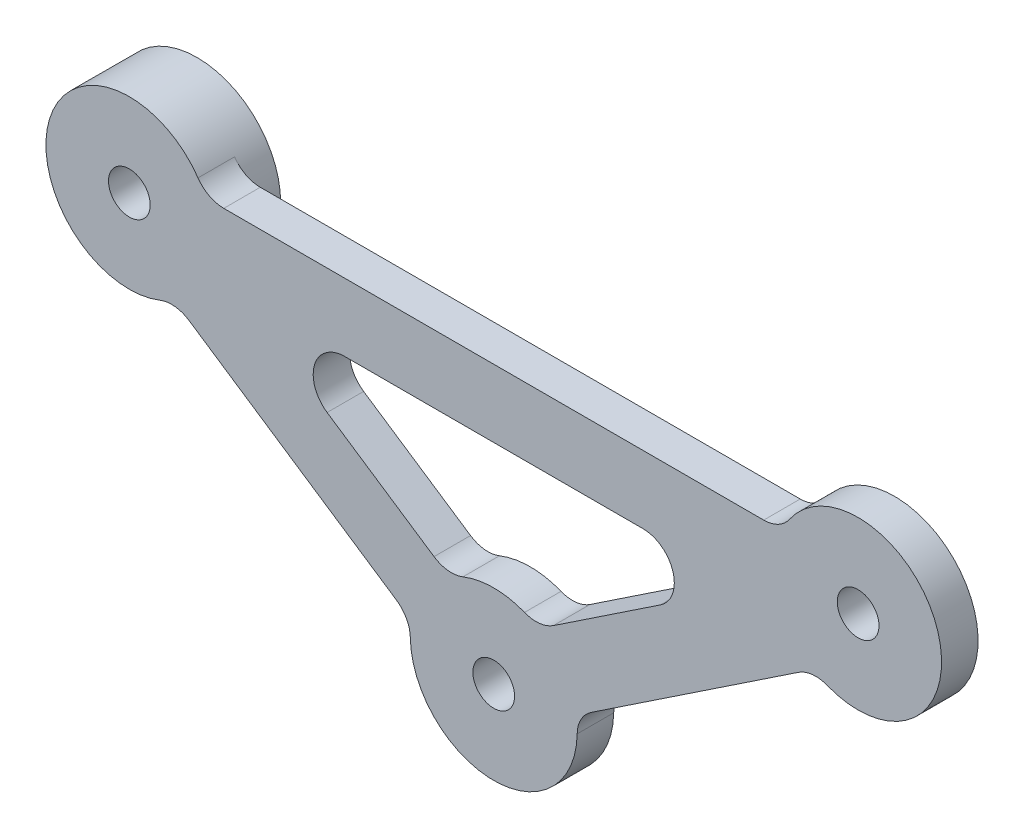
SolidWorks part; units mm, degrees
ref_plane "Front Plane" through (0, 0, 0) normal (0, 0, 1) x (1, 0, 0)
ref_plane "Top Plane" through (0, 0, 0) normal (0, 1, 0) x (1, 0, 0)
ref_plane "Right Plane" through (0, 0, 0) normal (1, 0, 0) x (0, 0, -1)
sketch "Sketch1" plane through (0, 0, 0) normal (0, 0, 1) x (1, 0, 0)
  line L0 (-29.6215, -38.3078) -> (5.3128, -61.623) construction
  line L1 (5.3128, -61.623) -> (40.247, -38.3078) construction
  line L2 (40.247, -38.3078) -> (-29.6215, -38.3078) construction
  circle A0 centre (-29.6215, -38.3078) radius 8
  circle A1 centre (40.247, -38.3078) radius 8
  circle A2 centre (5.3128, -61.623) radius 8
  circle A3 centre (-29.6215, -38.3078) radius 2
  circle A4 centre (40.247, -38.3078) radius 2
  circle A5 centre (5.3128, -61.623) radius 2
  dimension "D1" = 16
  dimension "D2" = 4
  dimension "D3" = 4
  dimension "D4" = 42
extrude "Boss-Extrude1" add sketch "Sketch1" against normal blind 3.5
sketch "Sketch4" plane through (0, 0, 0) normal (0, 0, 1) x (1, 0, 0)
  line L0 (35.3128, -38.3078) -> (-24.6872, -38.3078)
  line L1 (40.247, -38.3078) -> (-29.6215, -38.3078) construction
  line L2 (-24.6309, -41.6385) -> (0.3222, -58.2922)
  line L3 (-29.6215, -38.3078) -> (5.3128, -61.623) construction
  line L4 (10.3034, -58.2922) -> (35.2564, -41.6385)
  line L5 (5.3128, -61.623) -> (40.247, -38.3078) construction
  point P4 (5.3128, -38.3078)
  point P9 (-12.1544, -49.9654)
  point P14 (22.7799, -49.9654)
  dimension "D1" = 60
  dimension "D2" = 30
extrude "Extrude-Thin1" add sketch "Sketch4" against normal blind 3.5 thin thin type mid plane wall 6.5
fillet "Fillet1" radius 3 4 edges at (29.5228, -41.5578, -1.75) (-18.8973, -41.5578, -1.75) (9.5889, -54.8617, -1.75) (1.0366, -54.8617, -1.75)
sketch "草图1" plane through (0, 0, -3.5) normal (0, 0, -1) x (-1, 0, 0)
  circle A2 centre (29.6215, -38.3078) radius 2 construction
  arc A3 (25.3453, -45.0691) -> (22.3114, -35.0578) centre (29.6215, -38.3078) ccw construction
  circle A6 centre (29.6215, -38.3078) radius 2
  circle A7 centre (29.6215, -38.3078) radius 8
extrude "凸台-拉伸1" add sketch "草图1" along normal blind 3
fillet "圆角2" radius 3 6 edges at (-25.3453, -45.0691, -1.75) (-2.5717, -60.2682, -1.75) (13.1972, -60.2682, -1.75) (35.9709, -45.0691, -1.75) (32.9369, -35.0578, -1.75) (-22.3114, -35.0578, -1.75)
